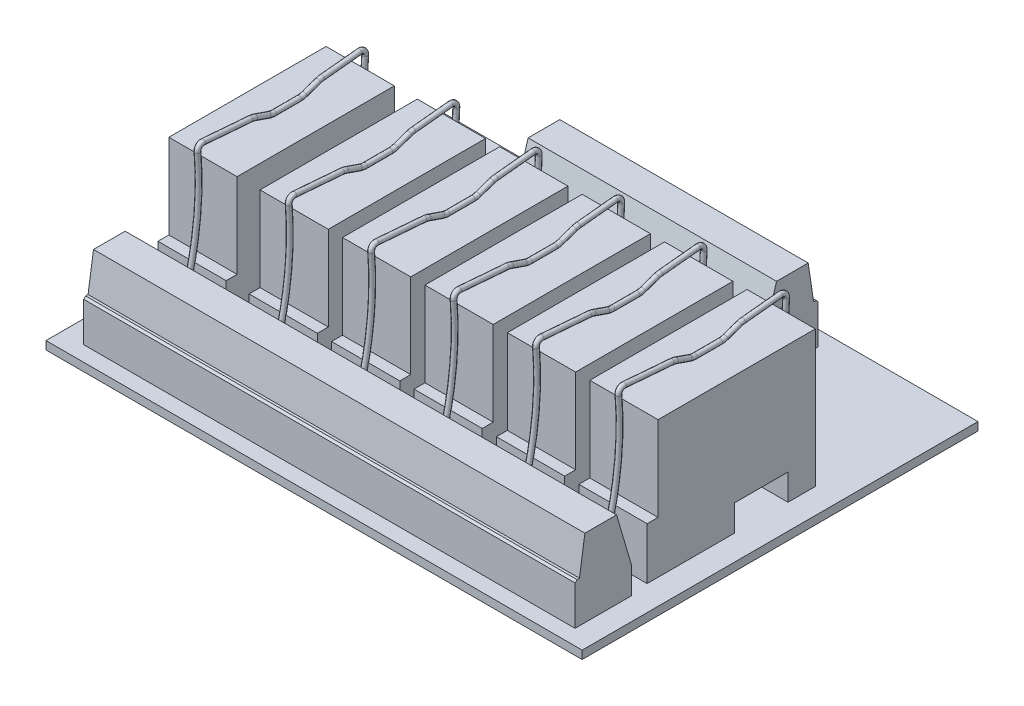
SolidWorks part; units mm, degrees
ref_plane "前基準面" through (0, 0, 0) normal (0, 0, 1) x (1, 0, 0)
ref_plane "上基準面" through (0, 0, 0) normal (0, 1, 0) x (1, 0, 0)
ref_plane "右基準面" through (0, 0, 0) normal (1, 0, 0) x (0, 0, -1)
sketch "草圖2" plane through (0, 0, 0) normal (0, 1, 0) x (1, 0, 0)
  line L1 (-49.1, 36.25) -> (49.1, 36.25)
  line L2 (-49.1, 36.25) -> (-49.1, -36.25)
  line L3 (-49.1, -36.25) -> (49.1, -36.25)
  line L4 (49.1, 36.25) -> (49.1, -36.25)
  line L5 (-49.1, 36.25) -> (49.1, -36.25) construction
  line L6 (-49.1, -36.25) -> (49.1, 36.25) construction
  point P0 (0, 0)
  dimension "D1" = 72.5
  dimension "D2" = 98.2
extrude "填料-伸長1" add sketch "草圖2" along normal blind 1.5
sketch "草圖3" plane through (0, 1.5, 0) normal (0, 1, 0) x (1, 0, 0)
  line L0 (-49.1, 36.25) -> (-49.1, -36.25) construction
  line L1 (-45.1, -17.75) -> (-32.6, -17.75)
  line L2 (-45.1, -17.75) -> (-45.1, 11.05)
  line L3 (-45.1, 11.05) -> (-32.6, 11.05)
  line L4 (-32.6, -17.75) -> (-32.6, 11.05)
  line L5 (-49.1, -36.25) -> (49.1, -36.25) construction
  line L6 (-28.4, -17.75) -> (-28.4, 11.05)
  line L7 (-45.1, -17.75) -> (-32.6, -17.75)
  line L8 (-45.1, -17.75) -> (-45.1, -19.75)
  line L9 (-45.1, -19.75) -> (-32.6, -19.75)
  line L10 (-32.6, -17.75) -> (-32.6, -19.75)
  line L11 (-28.4, -17.75) -> (-15.9, -17.75)
  line L12 (-15.9, -17.75) -> (-15.9, 11.05)
  line L13 (-28.4, 11.05) -> (-15.9, 11.05)
  line L14 (-28.4, -17.75) -> (-28.4, -19.75)
  line L15 (-28.4, -17.75) -> (-15.9, -17.75)
  line L16 (-15.9, -17.75) -> (-15.9, -19.75)
  line L17 (-28.4, -19.75) -> (-15.9, -19.75)
  line L18 (-13.3, -17.75) -> (-13.3, 11.05)
  line L19 (-13.3, 11.05) -> (-0.8, 11.05)
  line L20 (-0.8, -17.75) -> (-0.8, 11.05)
  line L21 (-13.3, -17.75) -> (-0.8, -17.75)
  line L22 (-13.3, -19.75) -> (-0.8, -19.75)
  line L23 (-13.3, -17.75) -> (-13.3, -19.75)
  line L24 (-0.8, -17.75) -> (-0.8, -19.75)
  line L25 (1.8, -17.75) -> (1.8, 11.05)
  line L26 (1.8, 11.05) -> (14.3, 11.05)
  line L27 (14.3, -17.75) -> (14.3, 11.05)
  line L28 (1.8, -17.75) -> (14.3, -17.75)
  line L29 (1.8, -19.75) -> (14.3, -19.75)
  line L30 (1.8, -17.75) -> (1.8, -19.75)
  line L31 (14.3, -17.75) -> (14.3, -19.75)
  line L32 (16.9, -17.75) -> (16.9, 11.05)
  line L33 (16.9, 11.05) -> (29.4, 11.05)
  line L34 (29.4, -17.75) -> (29.4, 11.05)
  line L35 (16.9, -17.75) -> (29.4, -17.75)
  line L36 (16.9, -19.75) -> (29.4, -19.75)
  line L37 (16.9, -17.75) -> (16.9, -19.75)
  line L38 (29.4, -17.75) -> (29.4, -19.75)
  line L39 (32, -17.75) -> (32, 11.05)
  line L40 (32, 11.05) -> (44.5, 11.05)
  line L41 (44.5, -17.75) -> (44.5, 11.05)
  line L42 (32, -17.75) -> (44.5, -17.75)
  line L43 (32, -19.75) -> (44.5, -19.75)
  line L44 (32, -17.75) -> (32, -19.75)
  line L45 (44.5, -17.75) -> (44.5, -19.75)
  line L46 (49.1, -36.25) -> (49.1, 36.25) construction
  point P42 (-38.85, 11.05)
  dimension "D1" = 28.8
  dimension "D2" = 12.5
  dimension "D3" = 4
  dimension "D4" = 18.5
  dimension "D5" = 30.8
  dimension "D7" = 16.7
  dimension "D9" = 4.6
  dimension "D6" = 2
  dimension "D8" = 5
extrude "填料-伸長2" add sketch "草圖3" along normal blind 25 contours L1 L4 L3 L2 | L13 L6 L11 L12 | L18 L21 L20 L19 | L25 L28 L27 L26 | L32 L35 L34 L33 | L39 L42 L41 L40 region at (-38.85, 1.5, 3.35) region at (-22.15, 1.5, 3.35) region at (-7.05, 1.5, 3.35) region at (8.05, 1.5, 3.35) region at (23.15, 1.5, 3.35) region at (38.25, 1.5, 3.35)
extrude "填料-伸長3" add sketch "草圖3<3>" along normal blind 9.5 contours L10 L1 L8 L9 | L14 L17 L16 L11 | L24 L21 L23 L22 | L31 L28 L30 L29 | L38 L35 L37 L36 | L45 L42 L44 L43 region at (-38.85, 1.5, 18.75) region at (-22.15, 1.5, 18.75) region at (-7.05, 1.5, 18.75) region at (8.05, 1.5, 18.75) region at (23.15, 1.5, 18.75) region at (38.25, 1.5, 18.75)
sketch "草圖3<3>" plane through (0, 1.5, 0) normal (0, 1, 0) x (1, 0, 0) same geometry as "草圖3"
sketch "草圖4" plane through (0, 0, 0) normal (1, 0, 0) x (0, 0, -1)
  line L0 (-19.75, 1.5) -> (11.05, 1.5) construction
  line L1 (-3.75, 1.5) -> (6.05, 1.5)
  line L2 (-3.75, 1.5) -> (-3.75, 6.3)
  line L3 (-3.75, 6.3) -> (6.05, 6.3)
  line L4 (6.05, 1.5) -> (6.05, 6.3)
  line L5 (11.05, 26.5) -> (11.05, 1.5) construction
  dimension "D1" = 4.8
  dimension "D2" = 5
  dimension "D3" = 9.8
extrude "除料-伸長1" cut sketch "草圖4" against normal through all both and the other way through all
ref_plane "平面1" through (-38.85, 0, 0) normal (-1, 0, 0) x (0, 0, 1)
sketch "草圖5" plane through (-38.85, 0, 0) normal (-1, 0, 0) x (0, 0, 1)
  line L0 (-9.3356, 8.4) -> (-11.3356, 8.4)
  line L1 (-11.05, 26.5) -> (-11.05, 1.5) construction
  line L2 (-10.9044, 28.9) -> (-4.068, 28.2)
  line L3 (-3.35, 28.0404) -> (-0.85, 27.1692)
  line L4 (0.15, 27) -> (4.75, 27)
  line L5 (5.75, 27.1692) -> (8.25, 28.0404)
  line L6 (9.0075, 28.2) -> (17.7527, 28.9)
  line L7 (19.75, 8.4) -> (17.75, 8.4)
  line L8 (-36.25, 1.5) -> (36.25, 1.5) construction
  line L9 (17.75, 26.5) -> (-11.05, 26.5) construction
  line L10 (19.75, 11) -> (19.75, 1.5) construction
  line L11 (17.75, 26.5) -> (17.75, 11) construction
  line L12 (77.2249, 23.0595) -> (18.55, 23.0595) construction
  line L13 (-193.3704, 17.4625) -> (-11.65, 17.4625) construction
  arc A0 (-11.3356, 8.4) -> (-11.85, 8.9391) centre (-11.3356, 8.9149) cw
  arc A1 (-11.95, 27.9) -> (-10.9044, 28.9) centre (-11.0012, 27.9546) cw
  arc A2 (-3.35, 28.0404) -> (-4.068, 28.2) centre (-4.3899, 25.0564) ccw
  arc A3 (-0.85, 27.1692) -> (0.15, 27) centre (0.15, 30.0389) ccw
  arc A4 (4.75, 27) -> (5.75, 27.1692) centre (4.75, 30.0389) ccw
  arc A5 (8.25, 28.0404) -> (9.0075, 28.2) centre (9.25, 25.1708) cw
  arc A6 (17.7527, 28.9) -> (18.75, 27.9) centre (17.8266, 27.9764) cw
  arc A7 (18.75, 27.9) -> (20.25, 9.038) centre (77.2249, 23.0595) ccw
  arc A8 (20.25, 9.038) -> (19.75, 8.4) centre (19.75, 8.9149) cw
  arc A9 (-11.95, 27.9) -> (-11.85, 8.9391) centre (-193.3704, 17.4625) cw
  point P7 (0, 0)
  dimension "D1" = 0.8
  dimension "D2" = 6.9
  dimension "D3" = 2.4
  dimension "D4" = 2.4
  dimension "D5" = 0.5
  dimension "D6" = 1
  dimension "D7" = 0.5
  dimension "D8" = 4.6
  dimension "D9" = 11.2
  dimension "D10" = 0.7
  dimension "D11" = 1
  dimension "D12" = 3.5
  dimension "D13" = 1
  dimension "D14" = 0.8
  dimension "D15" = 1
  dimension "D16" = 3.5
  dimension "D17" = 0.6
  dimension "D18" = 0.9
  dimension "D19" = 1
  dimension "D20" = 2
  dimension "D21" = 2
ref_plane "平面2" through (0, 0, 17.75) normal (0, 0, 1) x (1, 0, 0)
sketch "草圖6" plane through (0, 0, 17.75) normal (0, 0, 1) x (1, 0, 0)
  line L0 (-38.85, 9.038) -> (-38.85, 8.4) construction
  line L1 (-38.85, 9.038) -> (-38.85, 8.4) construction
  circle A0 centre (-38.85, 8.4) radius 0.45
  point P4 (-38.85, 8.2629)
  point P5 (-38.85, 8.4663)
  dimension "D1" = 0.9
sweep "掃出1" add profiles "草圖6" path "草圖5"
pattern_linear "直線複製排列1" count 2 spacing 16.7 along (1, 0, 0) of bodies 105
pattern_linear "直線複製排列2" count 5 spacing 15.1 along (1, 0, 0) of bodies 106
sketch "草圖7" plane through (0, 0, 0) normal (1, 0, 0) x (0, 0, -1)
  line L0 (-33.45, 1.5) -> (-33.45, 8.7)
  line L1 (-36.25, 1.5) -> (36.25, 1.5) construction
  line L2 (-33.45, 8.7) -> (-33.0964, 9.0536)
  line L3 (-33.0964, 9.0536) -> (-32.65, 9.0536)
  line L4 (-32.65, 9.0536) -> (-31.65, 15.7)
  line L5 (-31.65, 15.7) -> (-25.85, 15.7)
  line L6 (-25.85, 15.7) -> (-23.15, 6.5)
  line L7 (-23.15, 6.5) -> (-23.15, 1.5)
  line L8 (-23.15, 1.5) -> (-33.45, 1.5)
  line L9 (-36.25, 1.5) -> (-36.25, 0) construction
  line L10 (0, 37.4746) -> (0, 0) construction
  line L11 (23.15, 6.5) -> (23.15, 1.5)
  line L12 (25.85, 15.7) -> (23.15, 6.5)
  line L13 (31.65, 15.7) -> (25.85, 15.7)
  line L14 (32.65, 9.0536) -> (31.65, 15.7)
  line L15 (33.0964, 9.0536) -> (32.65, 9.0536)
  line L16 (33.45, 8.7) -> (33.0964, 9.0536)
  line L17 (33.45, 1.5) -> (33.45, 8.7)
  line L18 (23.15, 1.5) -> (33.45, 1.5)
  dimension "D1" = 7.2
  dimension "D2" = 14.2
  dimension "D3" = 5.8
  dimension "D4" = 5
  dimension "D5" = 10.3
  dimension "D6" = 0.8
  dimension "D7" = 135
  dimension "D8" = 0.5
  dimension "D9" = 1.8
  dimension "D10" = 2.8
extrude "填料-伸長4" add sketch "草圖7" along normal mid plane 90 contours L8 L7 L6 L5 L4 L3 L2 L0 region at (0, 7.9093, 28.4108)
extrude "填料-伸長5" add sketch "草圖7<3>" along normal blind 45.5 from offset 22.9 contours L11 L18 L17 L16 L15 L14 L13 L12 region at (0, 7.9093, -28.4108) offset against normal yes
sketch "草圖7<3>" plane through (0, 0, 0) normal (1, 0, 0) x (0, 0, -1) same geometry as "草圖7"
